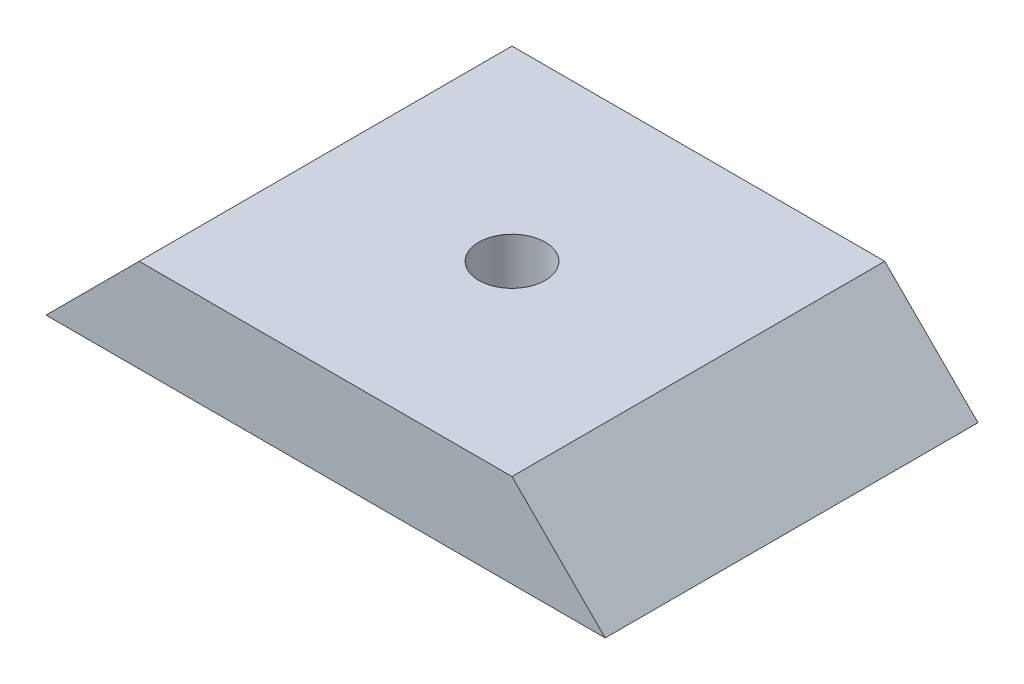
SolidWorks part; units mm, degrees
ref_plane "Front Plane" through (0, 0, 0) normal (0, 0, 1) x (1, 0, 0)
ref_plane "Top Plane" through (0, 0, 0) normal (0, 1, 0) x (1, 0, 0)
ref_plane "Right Plane" through (0, 0, 0) normal (1, 0, 0) x (0, 0, -1)
sketch "Sketch1" plane through (0, 0, 0) normal (0, 1, 0) x (1, 0, 0)
  line L1 (0, 0) -> (19.05, 0)
  line L2 (0, 0) -> (0, 12.7)
  line L3 (0, 12.7) -> (19.05, 12.7)
  line L4 (19.05, 0) -> (19.05, 12.7)
  dimension "D1" = 12.7
  dimension "D2" = 19.05
extrude "Boss-Extrude1" add sketch "Sketch1" along normal blind 3.175 contours L3 L4 L1 L2
chamfer "Chamfer1" distance 3.175 angle 45 2 edges at (19.05, 3.175, -6.35) (0, 3.175, -6.35)
hole_wizard "Tap Drill for #4-40 Tap1" positions "Sketch2" profile "Sketch3" hole size "#4-40" standard "ANSI Inch" end condition through all
sketch "Sketch2" plane through (0, 0, 0) normal (0, -1, 0) x (-1, 0, 0)
  line L1 (-9.525, 0) -> (-9.525, 12.7) construction
  line L2 (0, 0) -> (-19.05, 0) construction
  line L3 (0, 12.7) -> (-19.05, 12.7) construction
  point P0 (-9.525, 6.35)
  point P12 (0, 0)
  point P13 (-9.525, 6.35)
sketch "Sketch3" plane through (9.525, 0, -6.35) normal (1, 0, 0) x (0, 0, -1)
  line L0 (0, 0) -> (0, 3.175)
  line L1 (0, 3.175) -> (1.1303, 3.175)
  line L2 (1.1303, 3.175) -> (1.1303, 0)
  line L5 (1.1303, 0) -> (0, 0)
  line L11 (0, -6.35) -> (0, 107.95) construction
  dimension "Thru Hole Dia." = 2.2606
  dimension "Thru Hole Depth" = 3.175
equation "\"D2@Sketch1\"=.5in+.125*2in"
